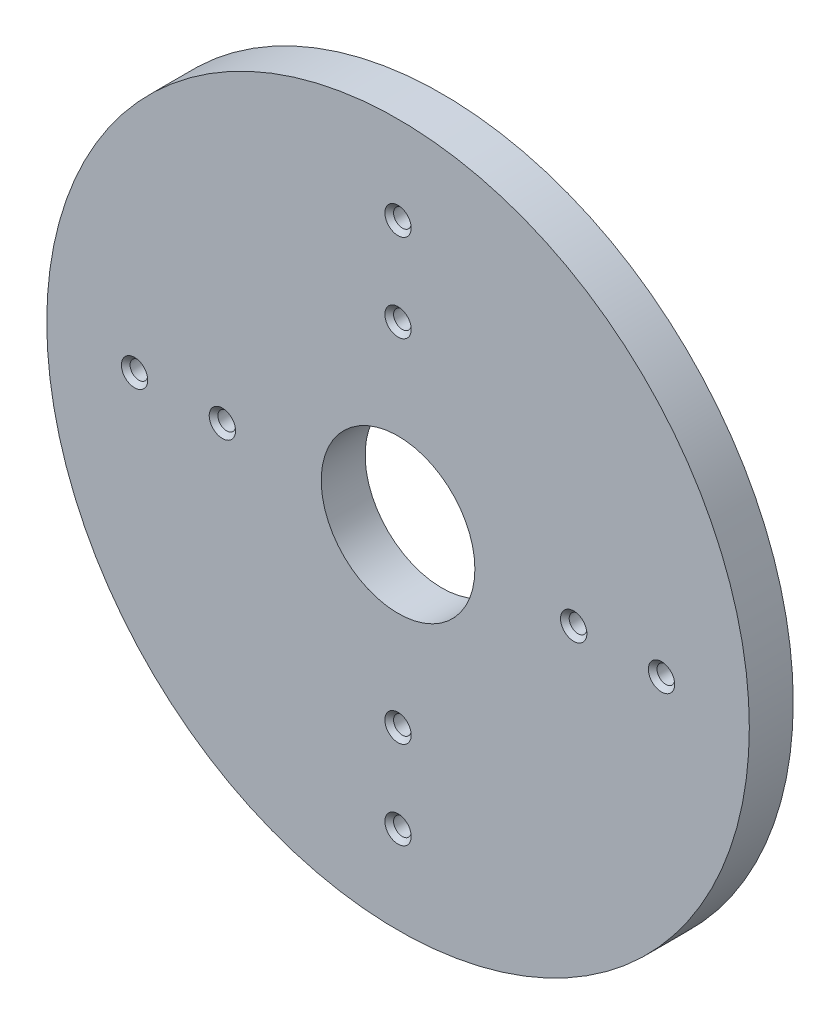
SolidWorks part; units mm, degrees
note: '?' marks a value the reader was unsure of.
material "6061-T6 (SS)"
ref_plane "Front Plane" through (0, 0, 0) normal (0, 0, 1) x (1, 0, 0)
ref_plane "Top Plane" through (0, 0, 0) normal (0, 1, 0) x (1, 0, 0)
ref_plane "Right Plane" through (0, 0, 0) normal (1, 0, 0) x (0, 0, -1)
sketch "Sketch1" plane through (0, 0, 0) normal (0, 0, 1) x (1, 0, 0)
  circle A0 centre (0, 0) radius 101.6
  circle A1 centre (0, 0) radius 22.225
  dimension "D1" = 203.2
  dimension "D2" = 44.45
extrude "Boss-Extrude1" add sketch "Sketch1" along normal blind 12.7
hole_wizard "1/4-20 Tapped Hole1" positions "Sketch2" profile "Sketch3" tap size "1/4-20" standard "ANSI Inch" end condition up to next
sketch "Sketch2" plane through (0, 0, 12.7) normal (0, 0, 1) x (1, 0, 0)
  line L0 (0, 0) -> (0, 76.2) construction
  point P2 (0, 76.2)
  point P8 (0, 50.8)
  point P13 (76.2, 0)
  point P14 (50.8, 0)
  point P15 (0, -76.2)
  point P16 (0, -50.8)
  point P17 (-76.2, 0)
  point P18 (-50.8, 0)
  dimension "D1" = 50.8
  dimension "D2" = 76.2
  dimension "D3" = 4
cosmetic thread "Hole Thread1"
cosmetic thread "Hole Thread2"
cosmetic thread "Hole Thread3"
cosmetic thread "Hole Thread4"
cosmetic thread "Hole Thread5"
cosmetic thread "Hole Thread6"
cosmetic thread "Hole Thread7"
cosmetic thread "Hole Thread8"
sketch "Sketch3" plane through (-50.8, 0, 12.7) normal (1, 0, 0) x (0, -1, 0)
  line L0 (0, 0) -> (0, 12.7)
  line L1 (0, 12.7) -> (3.81, 12.7)
  line L2 (2.5527, 11.4427) -> (2.5527, 1.2573)
  line L3 (2.5527, 1.2573) -> (3.81, 0)
  line L5 (3.81, 0) -> (0, 0)
  line L6 (-2.5527, 1.2573) -> (-3.81, 0) construction
  line L7 (3.81, 12.7) -> (2.5527, 11.4427)
  line L8 (-3.81, 12.7) -> (-2.5527, 11.4427) construction
  line L11 (0, -6.35) -> (0, 107.95) construction
  dimension "Thru Tap Drill Dia." = 5.1054
  dimension "Thru Tap Drill Depth" = 12.7
  dimension "Near C'Sink Dia." = 7.62
  dimension "Near C'Sink Angle" = 90
  dimension "Far C'Sink Dia." = 7.62
  dimension "Far C'Sink Angle" = 90
sketch "Sketch4" plane through (0, 0, 0) normal (0, 0, -1) x (-1, 0, 0)
  line L1 (101.6, 101.6) -> (-101.6, 101.6)
  line L2 (101.6, 101.6) -> (101.6, -101.6)
  line L3 (101.6, -101.6) -> (-101.6, -101.6)
  line L4 (-101.6, 101.6) -> (-101.6, -101.6)
  line L5 (0, -101.6) -> (0, 101.6) construction
  line L6 (101.6, 0) -> (-101.6, 0) construction
  circle A1 centre (0, 0) radius 22.225
  circle A2 centre (0, 0) radius 22.225 construction
  point P0 (0, 0)
  dimension "D1" = 203.2
extrude "Boss-Extrude2" [suppressed] add sketch "Sketch4" along normal blind 50.8 separate body
hole_wizard "CBORE for 1/4 Socket Head Cap Screw1" [suppressed] positions "Sketch5" profile "Sketch6" counterbore size "1/4" standard "ANSI Inch"
sketch "Sketch5" [suppressed] plane through (0, 0, 0) normal (0, 0, 1) x (1, 0, 0)
  line L1 (88.9, 88.9) -> (-88.9, 88.9) construction
  line L2 (88.9, 88.9) -> (88.9, -88.9) construction
  line L3 (88.9, -88.9) -> (-88.9, -88.9) construction
  line L4 (-88.9, 88.9) -> (-88.9, -88.9) construction
  line L5 (88.9, 88.9) -> (-88.9, -88.9) construction
  line L6 (88.9, -88.9) -> (-88.9, 88.9) construction
  point P2 (-88.9, -88.9)
  point P53 (88.9, 88.9)
  point P54 (88.9, -88.9)
  point P55 (-88.9, 88.9)
  point P61 (0, 0)
  dimension "D1" = 177.8
sketch "Sketch6" plane through (-88.9, -88.9, 0) normal (1, 0, 0) x (0, -1, 0)
  line L0 (0, 0) -> (0, 50.8)
  line L1 (3.2639, 50.165) -> (3.8989, 50.8)
  line L2 (5.5562, 44.45) -> (3.2639, 44.45)
  line L3 (3.2639, 44.45) -> (3.2639, 50.165)
  line L5 (5.5562, 44.45) -> (5.5562, 0.635)
  line L6 (5.5562, 0.635) -> (6.1913, 0)
  line L7 (6.1913, 0) -> (0, 0)
  line L8 (-5.5562, 0.635) -> (-6.1913, 0) construction
  line L11 (0, -6.35) -> (0, 107.95) construction
  line L12 (3.8989, 50.8) -> (0, 50.8)
  line L13 (-3.2639, 50.165) -> (-3.8989, 50.8) construction
  dimension "Thru Hole Dia." = 6.5278
  dimension "Thru Hole Depth" = 50.8
  dimension "C'Bore Dia." = 11.1125
  dimension "C'Bore Depth" = 44.45
  dimension "Near C'Sink Dia." = 12.3825
  dimension "Near C'Sink Angle" = 90
  dimension "Far C'Sink Dia." = 7.7978
  dimension "Far C'Sink Angle" = 90
sketch "Sketch7" [suppressed] plane through (0, -101.6, 0) normal (0, -1, 0) x (1, 0, 0)
  line L0 (101.6, -50.8) -> (-101.6, -50.8) construction
  line L1 (80.391, 17.653) -> (23.241, 17.653)
  line L2 (80.391, 17.653) -> (80.391, -39.497)
  line L3 (80.391, -39.497) -> (23.241, -39.497)
  line L4 (23.241, 17.653) -> (23.241, -39.497)
  line L5 (80.391, 17.653) -> (23.241, -39.497) construction
  line L6 (80.391, -39.497) -> (23.241, 17.653) construction
  circle A0 centre (51.816, -10.922) radius 19.05
  point P0 (51.816, -10.922)
  dimension "D4" = 38.1
  dimension "D1" = 57.15
  dimension "D2" = 51.816
  dimension "D3" = 39.878
extrude "Boss-Extrude3" [suppressed] add sketch "Sketch7" along normal blind 35.052
hole_wizard "#10-24 Tapped Hole1" [suppressed] positions "Sketch8" profile "Sketch10" tap size "#10-24" standard "ANSI Inch"
sketch "Sketch8" [suppressed] plane through (0, -136.652, 0) normal (0, -1, 0) x (-1, 0, 0)
  line L1 (-75.438, 34.544) -> (-28.194, 34.544) construction
  line L2 (-75.438, 34.544) -> (-75.438, -12.7) construction
  line L3 (-75.438, -12.7) -> (-28.194, -12.7) construction
  line L4 (-28.194, 34.544) -> (-28.194, -12.7) construction
  line L7 (-51.816, 29.972) -> (-51.816, -8.128) construction
  line L9 (-28.194, 34.544) -> (-75.438, -12.7) construction
  arc A3 (-36.2079, 0) -> (-67.4241, 0) centre (-51.816, 10.922) ccw construction
  circle A4 centre (-51.816, 10.922) radius 19.05 construction
  point P1 (-28.194, -12.7)
  point P170 (-75.438, 34.544)
  point P171 (-75.438, -12.7)
  point P172 (-28.194, 34.544)
  point P205 (-51.816, 10.922)
  dimension "D1" = 47.244
sketch "Sketch10" plane through (28.194, -136.652, 12.7) normal (1, 0, 0) x (0, 0, -1)
  line L0 (0, 0) -> (0, 26.5408)
  line L1 (0, 26.5408) -> (1.8986, 25.4)
  line L2 (1.8986, 25.4) -> (1.8986, 1.1494)
  line L3 (1.8986, 1.1494) -> (3.048, 0)
  line L5 (3.048, 0) -> (0, 0)
  line L6 (-1.8986, 1.1494) -> (-3.048, 0) construction
  line L10 (0, 26.5408) -> (-1.8987, 25.4) construction
  line L11 (0, -6.35) -> (0, 107.95) construction
  dimension "Tap Drill Dia." = 3.7973
  dimension "Tap Drill Depth" = 25.4
  dimension "Near C'Sink Dia." = 6.096
  dimension "Near C'Sink Angle" = 90
  dimension "Drill Angle" = 118
cosmetic thread "Hole Thread9" [suppressed] parameters "D1"=9.65, "D2"=4.826
cosmetic thread "Hole Thread10" [suppressed] parameters "D1"=9.65, "D2"=4.826
cosmetic thread "Hole Thread11" [suppressed] parameters "D1"=9.65, "D2"=4.826
cosmetic thread "Hole Thread12" [suppressed] parameters "D1"=9.65, "D2"=4.826
ref_axis "Axis1" through (0, 0, 12.7) along (0, 0, -1)?
